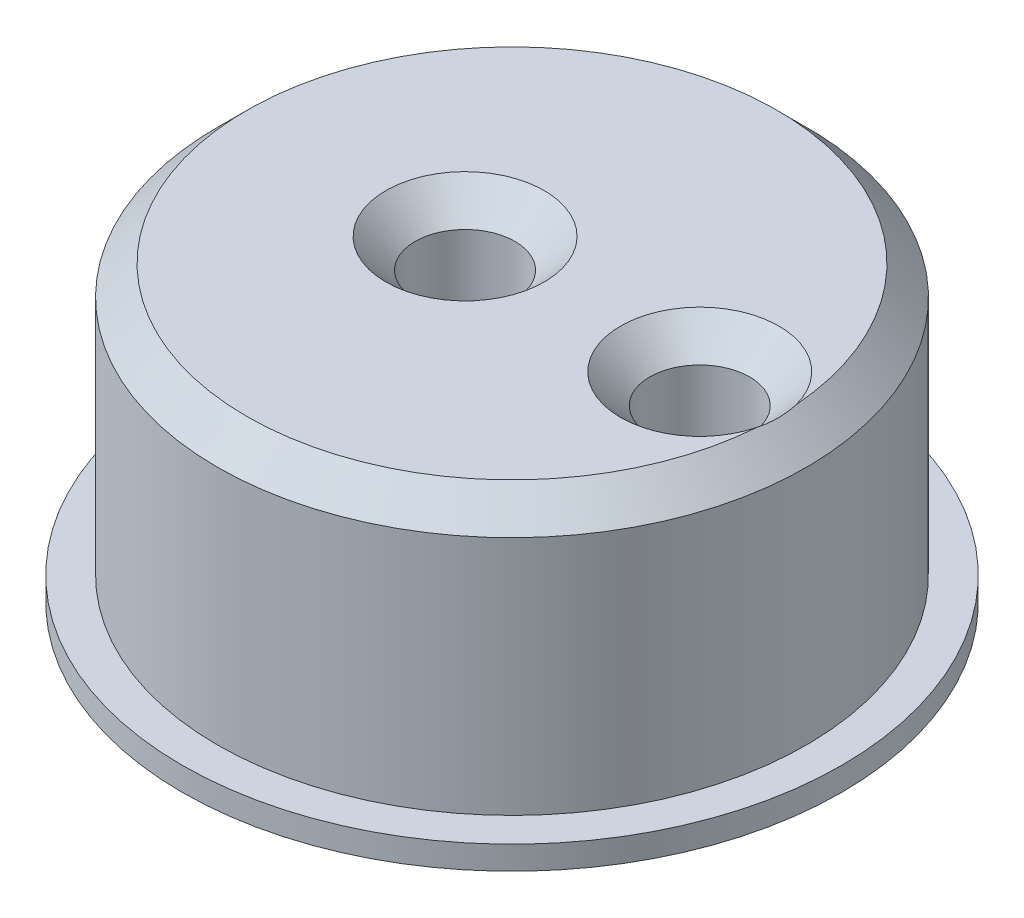
SolidWorks part; units mm, degrees
ref_plane "前视基准面" through (0, 0, 0) normal (0, 0, 1) x (1, 0, 0)
ref_plane "上视基准面" through (0, 0, 0) normal (0, 1, 0) x (1, 0, 0)
ref_plane "右视基准面" through (0, 0, 0) normal (1, 0, 0) x (0, 0, -1)
other "Configuration Table"
sketch "草图1" plane through (0, 0, 0) normal (0, 1, 0) x (1, 0, 0)
  line L0 (1.2, 6.4178) -> (1.2, -6.4114) construction
  line L1 (-5.7349, 0) -> (5.8104, 0) construction
  circle A0 centre (0, 0) radius 5.02
  circle A1 centre (3.2, 0) radius 0.85
  circle A2 centre (-0.8, 0) radius 0.85
  dimension "D1" = 10.04
  dimension "D3" = 4
  dimension "D4" = 1.7
  dimension "D2" = 1.2
extrude "凸台-拉伸1" add sketch "草图1" along normal blind 4.6
sketch "草图3" plane through (0, 0, 0) normal (0, -1, 0) x (1, 0, 0)
  circle A0 centre (3.2, 0) radius 0.85 construction
  circle A1 centre (0, 0) radius 5.02 construction
  circle A3 centre (-0.8, 0) radius 0.85 construction
  circle A4 centre (3.2, 0) radius 0.85
  circle A5 centre (-0.8, 0) radius 0.85
  circle A6 centre (0, 0) radius 5.02 construction
  circle A7 centre (0, 0) radius 5.62
  dimension "D1" = 0.6
extrude "凸台-拉伸2" add sketch "草图3" along normal blind 0.4
chamfer "倒角1" distance 0.5 angle 45 5 edges at (0, 4.6, 5.02) (-0.8, 4.6, -0.85) (3.2, 4.6, 0.85) (-0.8, -0.4, -0.85) (3.2, -0.4, -0.85)
ref_axis "基准轴1" through (0, 4.1, 0) along (0, -1, 0)
sketch "草图2" plane through (0, 0, 0) normal (0, 1, 0) x (1, 0, 0)
  line L0 (-5.9042, 0) -> (6.2358, 0) construction
